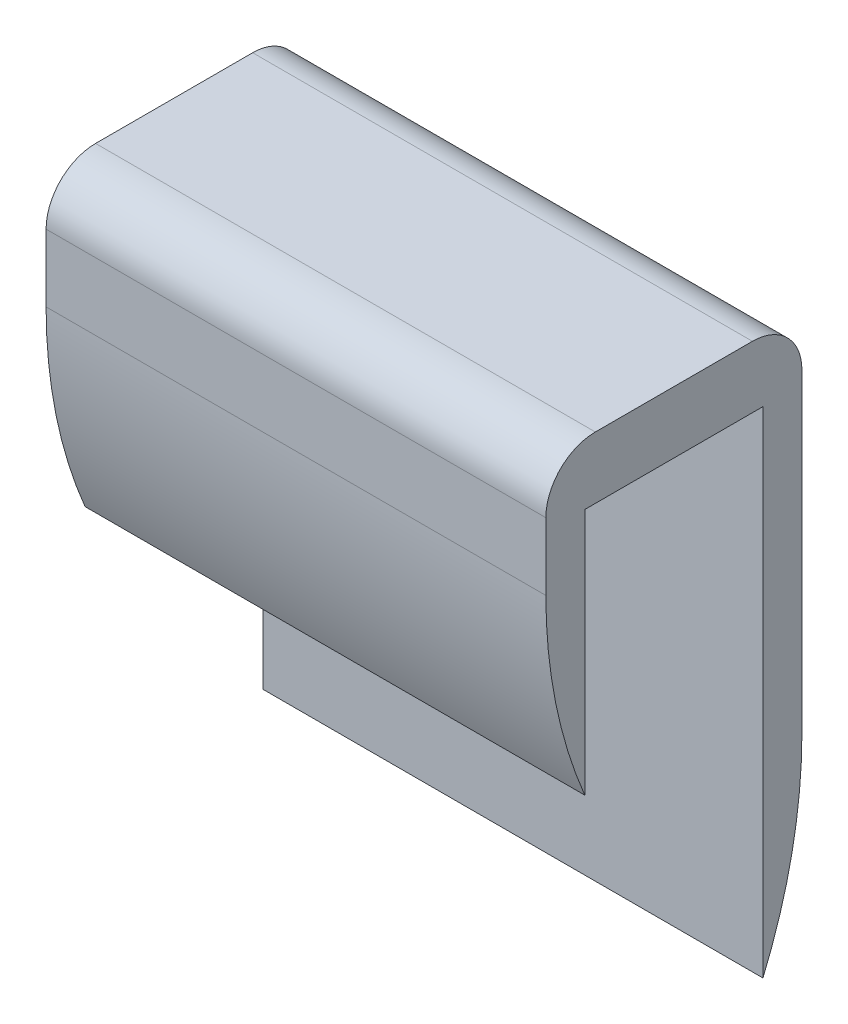
SolidWorks part; units mm, degrees
ref_plane "Front Plane" through (0, 0, 0) normal (0, 0, 1) x (1, 0, 0)
ref_plane "Top Plane" through (0, 0, 0) normal (0, 1, 0) x (1, 0, 0)
ref_plane "Right Plane" through (0, 0, 0) normal (1, 0, 0) x (0, 0, -1)
sketch "Sketch1" plane through (0, 0, 0) normal (1, 0, 0) x (0, 0, -1)
  line L0 (-6.572, -12.7) -> (-4.572, -12.7)
  line L1 (-4.572, -12.7) -> (-4.572, 0)
  line L2 (-4.572, 0) -> (4.572, 0)
  line L3 (4.572, 0) -> (4.572, -25.4)
  line L4 (4.572, -25.4) -> (6.572, -25.4)
  line L5 (6.572, -25.4) -> (6.572, 3.175)
  line L6 (6.572, 3.175) -> (-6.572, 3.175)
  line L7 (-6.572, 3.175) -> (-6.572, -12.7)
  point P6 (0, 0)
  dimension "D1" = 2
  dimension "D2" = 12.7
  dimension "D3" = 3.175
  dimension "D4" = 9.144
  dimension "D5" = 25.4
extrude "Boss-Extrude1" add sketch "Sketch1" along normal blind 25.654
fillet "Fillet1" radius 25.4 2 edges at (12.827, -12.7, 6.572) (12.827, -25.4, -6.572)
fillet "Fillet2" radius 2.54 2 edges at (12.827, 3.175, -6.572) (12.827, 3.175, 6.572)
equation "\"Height\"= 12in"
equation "\"Depth\"= 7in"
equation "\"WallThickness\"= 0.1875in"
equation "\"FloorThickness\"= 0.1875in"
equation "\"Width\" = 30in"
equation "\"D4@Sketch1\"=\"WallThickness\"*2-.015"
